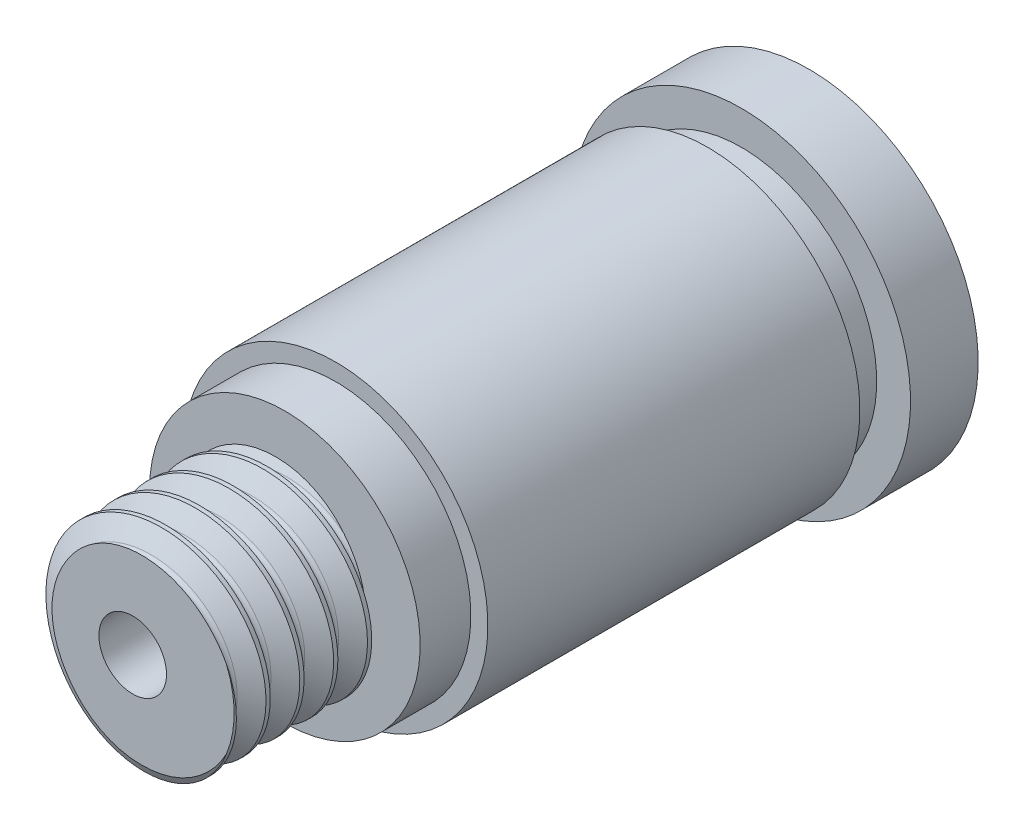
SolidWorks part; units mm, degrees
material "Stainless Steel (ferritic)"
ref_plane "Front Plane" through (0, 0, 0) normal (0, 0, 1) x (1, 0, 0)
ref_plane "Top Plane" through (0, 0, 0) normal (0, 1, 0) x (1, 0, 0)
ref_plane "Right Plane" through (0, 0, 0) normal (1, 0, 0) x (0, 0, -1)
sketch "Sketch1" plane through (0, 0, 0) normal (0, 0, 1) x (1, 0, 0)
  circle A0 centre (0, 0) radius 3
extrude "Boss-Extrude1" add sketch "Sketch1" along normal blind 4.5
sketch "Sketch2" plane through (0, 0, 4.5) normal (0, 0, 1) x (1, 0, 0)
  circle A0 centre (0, 0) radius 3
curve "Helix/Spiral1" pitch 1 height 6.25 turns 6.25
sketch "Sketch3" plane through (0, 0, 0) normal (0, 1, 0) x (1, 0, 0)
  line L0 (-3, -4.5) -> (3, -4.5) construction
  line L4 (-2.4588, -4.3753) -> (-3.0222, -4.05)
  line L5 (-3.0222, -4.05) -> (-3.0222, -4.95)
  line L6 (-3.0222, -4.95) -> (-2.4588, -4.6247)
  arc A0 (-2.4588, -4.3753) -> (-2.4588, -4.6247) centre (-2.5308, -4.5) cw
  circle A1 centre (-2.7624, -4.5) radius 0.2598 construction
  dimension "D1" = 0.144
sweep "Cut-Sweep2" cut profiles "Sketch3" path "Helix/Spiral1"
sketch "Sketch4" plane through (0, 0, 0) normal (0, 0, -1) x (-1, 0, 0)
  circle A1 centre (0, 0) radius 4
extrude "Boss-Extrude2" add sketch "Sketch4" along normal blind 1.5
sketch "Sketch5" plane through (0, 0, -1.5) normal (0, 0, -1) x (-1, 0, 0)
  circle A0 centre (0, 0) radius 4.5026
extrude "Boss-Extrude3" add sketch "Sketch5" along normal blind 11
sketch "Sketch6" plane through (0, 0, -12.5) normal (0, 0, -1) x (-1, 0, 0)
  circle A0 centre (0, 0) radius 4
extrude "Boss-Extrude4" add sketch "Sketch6" along normal blind 1
sketch "Sketch7" plane through (0, 0, -13.5) normal (0, 0, -1) x (-1, 0, 0)
  circle A0 centre (0, 0) radius 5
extrude "Boss-Extrude5" add sketch "Sketch7" along normal blind 2
sketch "Sketch9" plane through (0, 0, 4.5) normal (0, 0, 1) x (1, 0, 0)
  circle A0 centre (0, 0) radius 1
extrude "Cut-Extrude1" cut sketch "Sketch9" against normal blind 51
sketch "Sketch10" plane through (0, 0, -15.5) normal (0, 0, -1) x (-1, 0, 0)
  circle A0 centre (0, 0) radius 2
extrude "Cut-Extrude2" cut sketch "Sketch10" against normal blind 10
